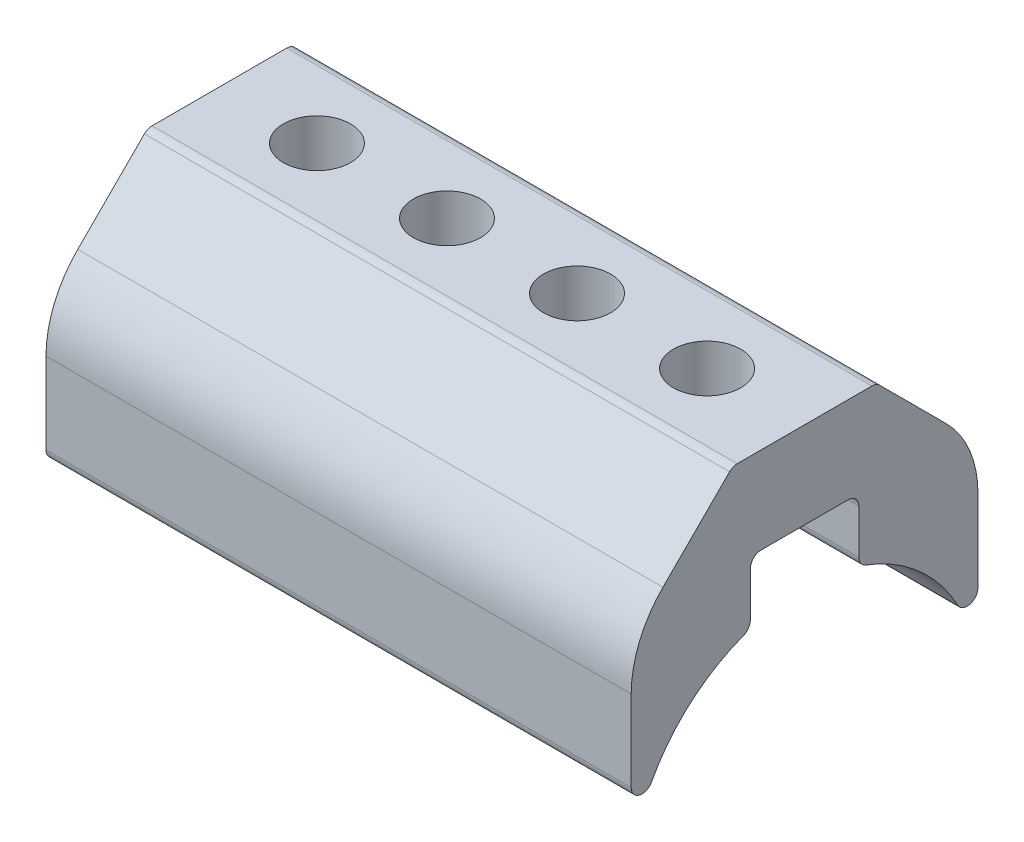
SolidWorks part; units mm, degrees
ref_plane "Front" through (0, 0, 0) normal (0, 0, 1) x (1, 0, 0)
ref_plane "Top" through (0, 0, 0) normal (0, 1, 0) x (1, 0, 0)
ref_plane "Right" through (0, 0, 0) normal (1, 0, 0) x (0, 0, -1)
sketch "Sketch1" plane through (0, 0, 0) normal (1, 0, 0) x (0, 0, -1)
  line L0 (0, 0) -> (0, 50000) construction
  line L1 (0, 0) -> (50000, 0) construction
  line L2 (16, 8) -> (16, 19.6274)
  line L3 (16, 19.6274) -> (6.6274, 29)
  line L4 (6.6274, 29) -> (-6.6274, 29)
  line L5 (0.1598, 16) -> (-49999.8402, 16) construction
  line L6 (-16, 19.6274) -> (-6.6274, 29)
  line L7 (-16, 8) -> (-16, 19.6274)
  arc A0 (14.1176, 7.5294) -> (-14.1176, 7.5294) centre (0, 0) ccw
  arc A1 (16, 8) -> (14.1176, 7.5294) centre (15, 8) cw
  arc A2 (-16, 8) -> (-14.1176, 7.5294) centre (-15, 8) ccw
  point P15 (16, 0)
  point P19 (0, 29)
  dimension "D2" = 32
  dimension "D4" = 1
  dimension "D1" = 225
  dimension "D3" = 13
extrude "Boss-Extrude1" add sketch "Sketch1" along normal blind 54
sketch "Sketch2" plane through (0, 29, 0) normal (0, 1, 0) x (1, 0, 0)
  line L0 (0, 0) -> (-50000, 0) construction
  circle A0 centre (9, 0) radius 3.1
  circle A1 centre (9, 0) radius 2
  circle A2 centre (21, 0) radius 2
  circle A3 centre (21, 0) radius 3.1
  circle A4 centre (33, 0) radius 2
  circle A5 centre (33, 0) radius 3.1
  circle A6 centre (45, 0) radius 2
  circle A7 centre (45, 0) radius 3.1
  dimension "D1" = 4
  dimension "D2" = 6.2
  dimension "D4" = 9
  dimension "D3" = 4
extrude "Cut-Extrude1" cut sketch "Sketch2" against normal through all both and the other way through all contours A1 L0 | L0 A1 | L0 A2 | A2 L0 | L0 A4 | A4 L0 | L0 A6 | A6 L0 region at (9, 29, 0) region at (21, 29, 0) region at (33, 29, 0) region at (45, 29, 0)
extrude "Cut-Extrude2" cut sketch "Sketch2<4>" against normal blind 5 contours L0 A0 A1 | A0 L0 A1 | A3 L0 A2 | L0 A3 A2 | L0 A5 A4 | A5 L0 A4 | L0 A7 A6 | A7 L0 A6 region at (5.9877, 29, 0) region at (17.9877, 29, 0) region at (29.9877, 29, 0) region at (41.9877, 29, 0)
sketch "Sketch2<4>" plane through (0, 29, 0) normal (0, 1, 0) x (1, 0, 0) same geometry as "Sketch2"
sketch "Sketch4" plane through (0, 0, 0) normal (-1, 0, 0) x (0, 0, 1)
  line L0 (0, 0) -> (0, 50000) construction
  line L2 (-5, 11) -> (5, 11)
  line L3 (-5, 11) -> (-5, 21)
  line L4 (-5, 21) -> (5, 21)
  line L5 (5, 11) -> (5, 21)
  line L6 (-5, 11) -> (5, 21) construction
  line L7 (-5, 21) -> (5, 11) construction
  arc A0 (14.1176, 7.5294) -> (-14.1176, 7.5294) centre (0, 0) ccw construction
  arc A1 (14.1176, 7.5294) -> (-14.1176, 7.5294) centre (0, 0) ccw construction
  arc A2 (14.1176, 7.5294) -> (-14.1176, 7.5294) centre (0, 0) ccw
  point P3 (0, 16)
  arc M14 (-14.1176, 7.5294) -> (14.1176, 7.5294) centre (0, 0) cw
  dimension "D1" = 10
  dimension "D2" = 10
extrude "Cut-Extrude7" cut sketch "Sketch4" against normal through all both and the other way through all contours L5 L4 L3 M14 region at (0, 18.3624, 0)
fillet "Fillet1" radius 1 6 edges at (27, 21, -5) (27, 21, 5) (27, 29, -6.6274) (27, 29, 6.6274)
fillet "Fillet2" radius 10 2 edges at (27, 19.6274, -16) (27, 19.6274, 16)
